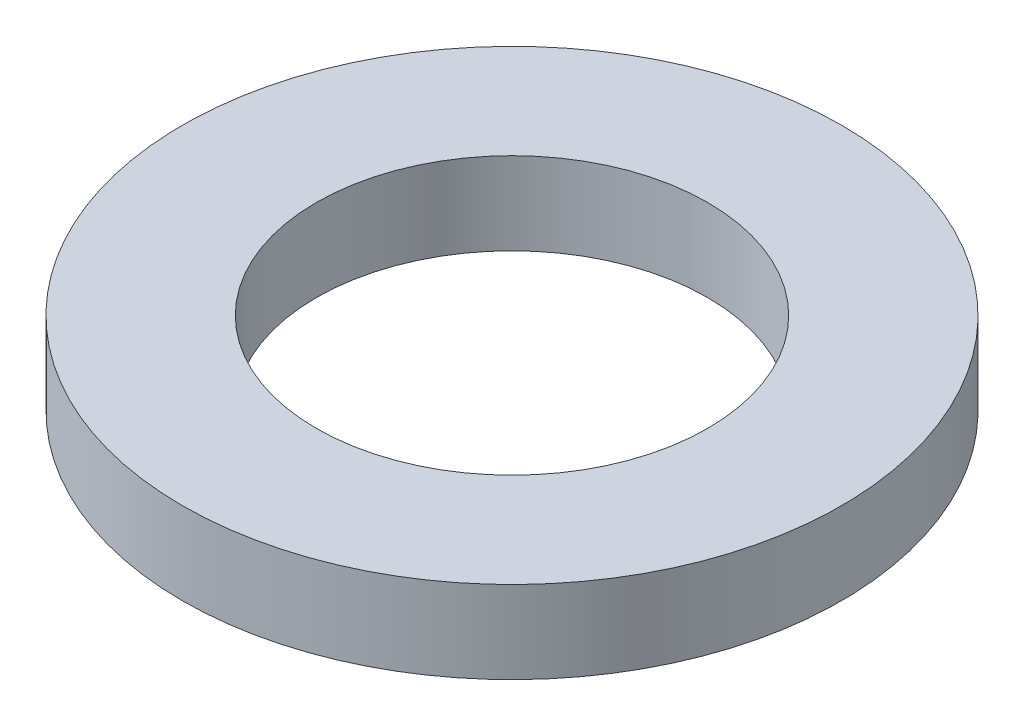
SolidWorks part; units mm, degrees
ref_plane "Front Plane" through (0, 0, 0) normal (0, 0, 1) x (1, 0, 0)
ref_plane "Top Plane" through (0, 0, 0) normal (0, 1, 0) x (1, 0, 0)
ref_plane "Right Plane" through (0, 0, 0) normal (1, 0, 0) x (0, 0, -1)
sketch "Sketch1" plane through (0, 0, 0) normal (0, 1, 0) x (1, 0, 0)
  circle A0 centre (0, 0) radius 80
  dimension "FLANGE_OD" = 160
extrude "Boss-Extrude1" add sketch "Sketch1" along normal blind 20
sketch "Sketch2" plane through (0, 0, 0) normal (0, 1, 0) x (1, 0, 0)
  circle A0 centre (0, 0) radius 47.5
  dimension "BORE_D" = 95
extrude "Cut-Extrude1" cut sketch "Sketch2" along normal through all
sketch "Sketch3" plane through (0, 20, 0) normal (0, 1, 0) x (1, 0, 0)
  circle A0 centre (0, 0) radius 31.3213 construction
  circle A1 centre (-31.3213, 0) radius 4.2012
  dimension "BOLT_D" = 8.4024
  dimension "BOLT_PCD" = 62.6426
extrude "Cut-Extrude2" cut sketch "Sketch3" against normal blind 12.7652 rebuild error yes
pattern_circular "CirPattern1" count 3 over 360 rebuild error yes
